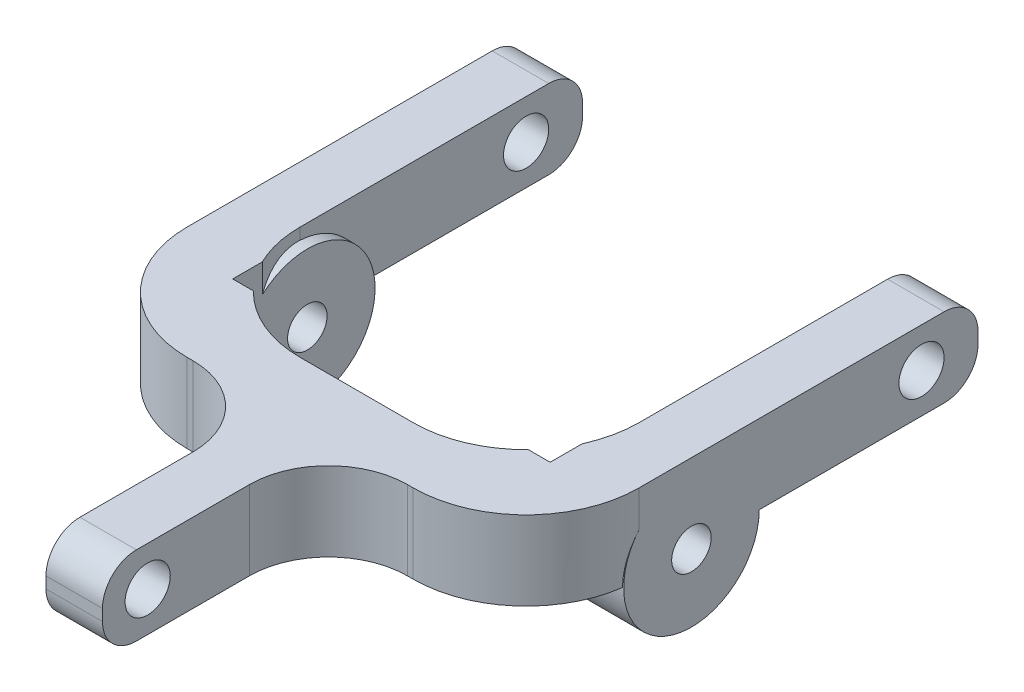
SolidWorks part; units mm, degrees
ref_plane "Front Plane" through (0, 0, 0) normal (0, 0, 1) x (1, 0, 0)
ref_plane "Top Plane" through (0, 0, 0) normal (0, 1, 0) x (1, 0, 0)
ref_plane "Right Plane" through (0, 0, 0) normal (1, 0, 0) x (0, 0, -1)
sketch "Sketch1" plane through (0, 0, 0) normal (1, 0, 0) x (0, 0, -1)
  line L1 (-20, 3.5) -> (20, 3.5)
  line L2 (-20, 3.5) -> (-20, -3.5)
  line L3 (-20, -3.5) -> (20, -3.5)
  line L4 (20, 3.5) -> (20, -3.5)
  line L5 (-20, 3.5) -> (20, -3.5) construction
  line L6 (-20, -3.5) -> (20, 3.5) construction
  point P0 (0, 0)
  dimension "D1" = 7
  dimension "D2" = 40
extrude "Boss-Extrude1" add sketch "Sketch1" along normal blind 40
sketch "Sketch2" plane through (0, 3.5, 0) normal (0, 1, 0) x (1, 0, 0)
  line L0 (40, 20) -> (0, 20) construction
  line L1 (5, 20) -> (35, 20)
  line L2 (5, 20) -> (5, -5)
  line L3 (15, -15) -> (25, -15)
  line L4 (35, 20) -> (35, -5)
  line L5 (0, 20) -> (0, -20) construction
  line L6 (40, 20) -> (40, -20) construction
  arc A0 (25, -15) -> (35, -5) centre (25, -5) ccw
  arc A1 (5, -5) -> (15, -15) centre (15, -5) ccw
  point P14 (5, -15)
  dimension "D4" = 10
  dimension "D1" = 5
  dimension "D2" = 5
  dimension "D3" = 35
extrude "Cut-Extrude1" cut sketch "Sketch2" against normal through all
fillet "Fillet1" radius 10 2 edges at (40, 0, 20) (0, 0, 20)
sketch "Sketch5" plane through (0, 0, 20) normal (0, 0, 1) x (1, 0, 0)
  line L0 (30, 3.5) -> (10, 3.5) construction
  line L1 (17.5, 3.5) -> (22.5, 3.5)
  line L2 (17.5, 3.5) -> (17.5, -3.5)
  line L3 (17.5, -3.5) -> (22.5, -3.5)
  line L4 (22.5, 3.5) -> (22.5, -3.5)
  line L5 (30, -3.5) -> (10, -3.5) construction
  line L6 (20, 3.5) -> (20, -3.5) construction
  point P10 (20, -3.5)
  dimension "D1" = 5
extrude "Boss-Extrude2" add sketch "Sketch5" along normal blind 20
fillet "Fillet2" radius 7 2 edges at (22.5, 0, 20) (17.5, 0, 20)
fillet "Fillet3" radius 3 6 edges at (2.5, -3.5, -20) (2.5, 3.5, -20) (37.5, -3.5, -20) (37.5, 3.5, -20) (20, -3.5, 40) (20, 3.5, 40)
sketch "Sketch6" plane through (40, 0, 0) normal (1, 0, 0) x (0, 0, -1)
  line L0 (15, 0) -> (0, 0) construction
  circle A0 centre (15, 0) radius 2
  dimension "D1" = 15
extrude "Cut-Extrude2" cut sketch "Sketch6" against normal through all
sketch "Sketch7" plane through (22.5, 0, 0) normal (1, 0, 0) x (0, 0, -1)
  line L0 (0, 0) -> (-36, 0) construction
  circle A0 centre (-36, 0) radius 2
  dimension "D1" = 36
extrude "Cut-Extrude3" cut sketch "Sketch7" against normal through all
sketch "Sketch8" plane through (40, 0, 0) normal (1, 0, 0) x (0, 0, -1)
  line L0 (-10, -3.5) -> (17, -3.5) construction
  circle A0 centre (-5.366, -3.5) radius 6
extrude "Boss-Extrude3" add sketch "Sketch8" against normal blind 40
sketch "Sketch9" plane through (0, 0, 0) normal (0, 1, 0) x (1, 0, 0)
  line L1 (5.9985, -11.972) -> (34.1001, -11.972)
  line L2 (5.9985, -11.972) -> (5.9985, 2.2267)
  line L3 (5.9985, 2.2267) -> (34.1001, 2.2267)
  line L4 (34.1001, -11.972) -> (34.1001, 2.2267)
extrude "Cut-Extrude4" cut sketch "Sketch9" against normal through all and the other way through all
sketch "Sketch10" plane through (40, 0, 0) normal (1, 0, 0) x (0, 0, -1)
  circle A0 centre (-5.366, -3.5) radius 1.75
  dimension "D1" = 3.5
extrude "Cut-Extrude5" cut sketch "Sketch10" against normal through all
